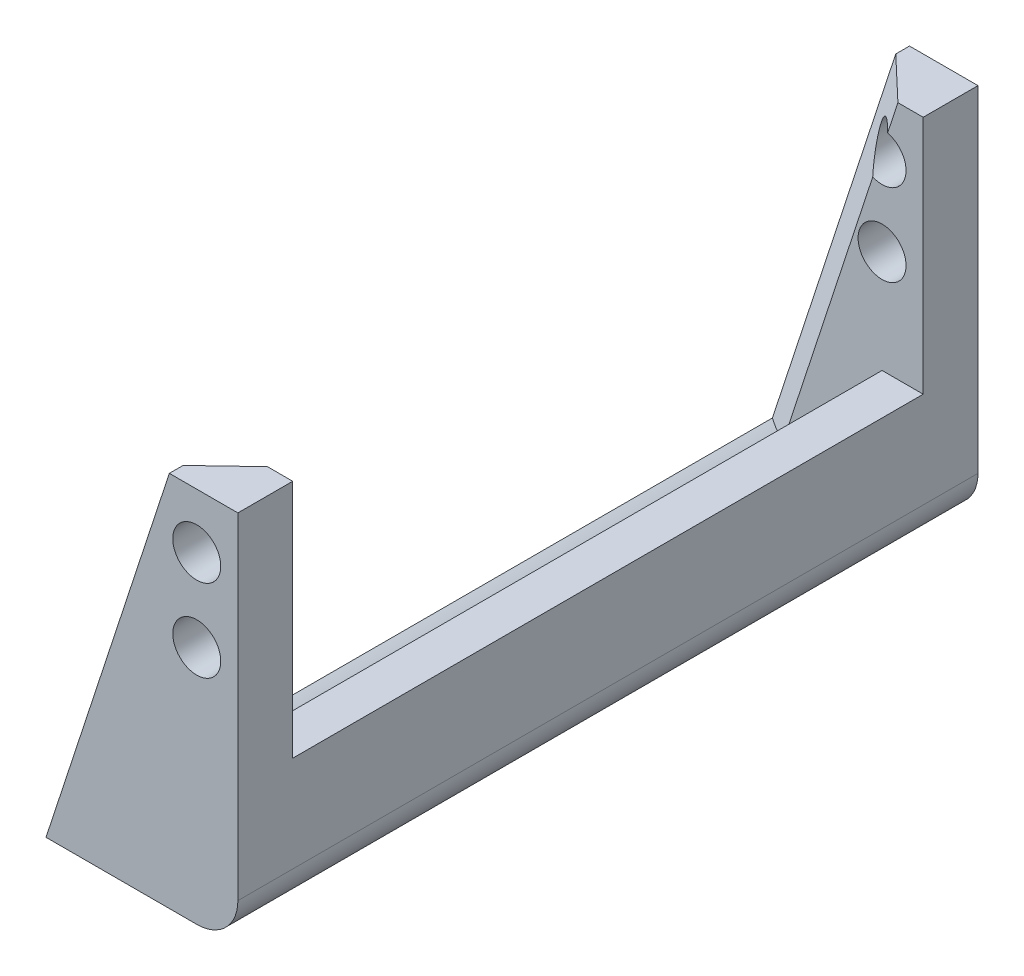
SolidWorks part; units mm, degrees
ref_plane "Front Plane" through (0, 0, 0) normal (0, 0, 1) x (1, 0, 0)
ref_plane "Top Plane" through (0, 0, 0) normal (0, 1, 0) x (1, 0, 0)
ref_plane "Right Plane" through (0, 0, 0) normal (1, 0, 0) x (0, 0, -1)
sketch "Sketch1" plane through (0, 0, 0) normal (0, 0, 1) x (1, 0, 0)
  line L0 (0, 0) -> (14, 0)
  line L1 (14, 0) -> (14, 10)
  line L2 (11, 10) -> (14, 10)
  arc A0 (0, 0) -> (11, 10) centre (-8.0707, 19.9277) ccw
  circle A1 centre (-8.0707, 19.9277) radius 21.5 construction
  dimension "D3" = 21.5
  dimension "D1" = 10
  dimension "D2" = 14
  dimension "D4" = 3
extrude "Boss-Extrude1" add sketch "Sketch1" along normal mid plane 46
sketch "Sketch2" plane through (0, 0, 23) normal (0, 0, 1) x (1, 0, 0)
  line L0 (14, 0) -> (14, 27.5)
  line L1 (14, 27.5) -> (9, 27.5)
  line L2 (9, 27.5) -> (0, 0)
  line L3 (0, 0) -> (14, 0)
  line L4 (11, 27.5) -> (11, 23.5) construction
  line L5 (11, 23.5) -> (11, 17.5) construction
  circle A0 centre (11, 23.5) radius 1.75
  circle A1 centre (11, 17.5) radius 1.75
  point P6 (0, 0)
  dimension "D5" = 3.5
  dimension "D1" = 27.5
  dimension "D2" = 5
  dimension "D3" = 4
  dimension "D4" = 6
  dimension "D6" = 3
extrude "Boss-Extrude2" add sketch "Sketch2" along normal blind 4
mirror "Mirror1" about plane through (0, 0, 0) normal (0, 0, 1) of "Boss-Extrude2"
fillet "Fillet1" radius 3 1 edges at (14, 0, 0)
chamfer "Chamfer1" distance 3 angle 45 2 edges at (4.5, 13.75, 23) (4.5, 13.75, -23)
